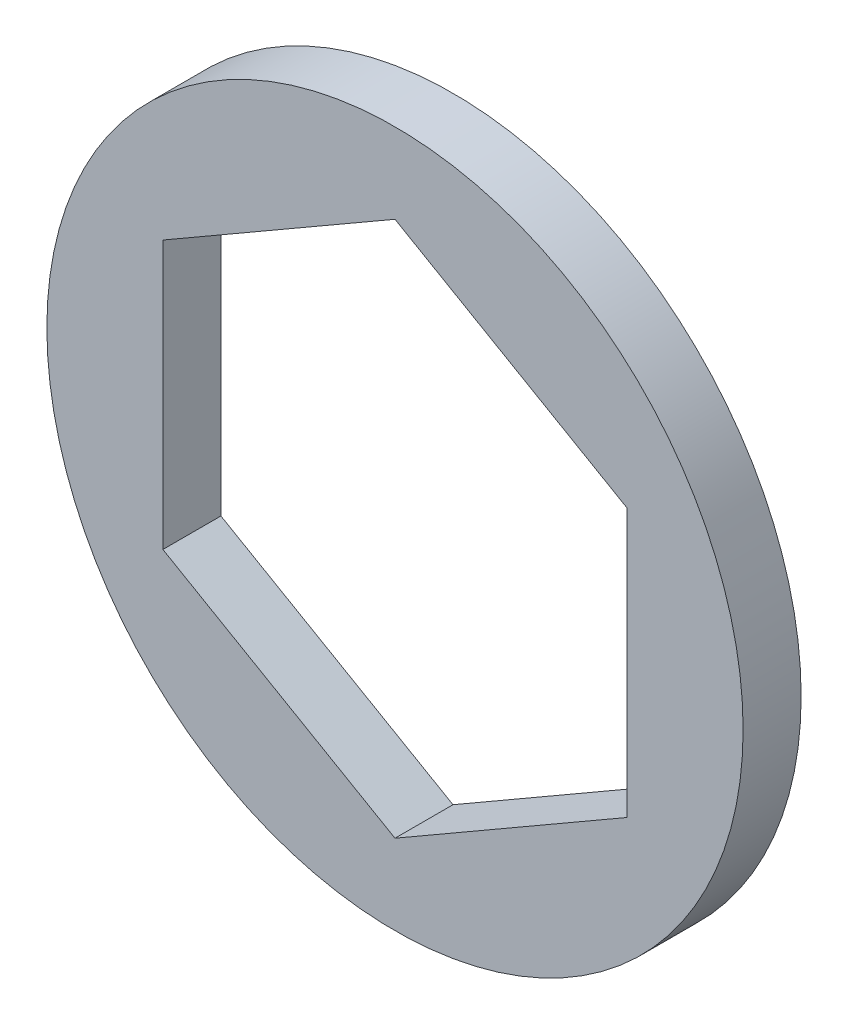
SolidWorks part; units mm, degrees
material "PET"
ref_plane "Front Plane" through (0, 0, 0) normal (0, 0, 1) x (1, 0, 0)
ref_plane "Top Plane" through (0, 0, 0) normal (0, 1, 0) x (1, 0, 0)
ref_plane "Right Plane" through (0, 0, 0) normal (1, 0, 0) x (0, 0, -1)
sketch "Sketch1" plane through (0, 0, 0) normal (0, 0, 1) x (1, 0, 0)
  line L1 (0, 7.3323) -> (-6.35, 3.6662)
  line L2 (-6.35, 3.6662) -> (-6.35, -3.6662)
  line L3 (-6.35, -3.6662) -> (0, -7.3323)
  line L4 (0, -7.3323) -> (6.35, -3.6662)
  line L5 (6.35, -3.6662) -> (6.35, 3.6662)
  line L6 (6.35, 3.6662) -> (0, 7.3323)
  circle A0 centre (0, 0) radius 6.35 construction
  circle A1 centre (0, 0) radius 9.525
  dimension "D1" = 12.7
  dimension "D2" = 19.05
extrude "Boss-Extrude1" add sketch "Sketch1" along normal mid plane 1.5875
